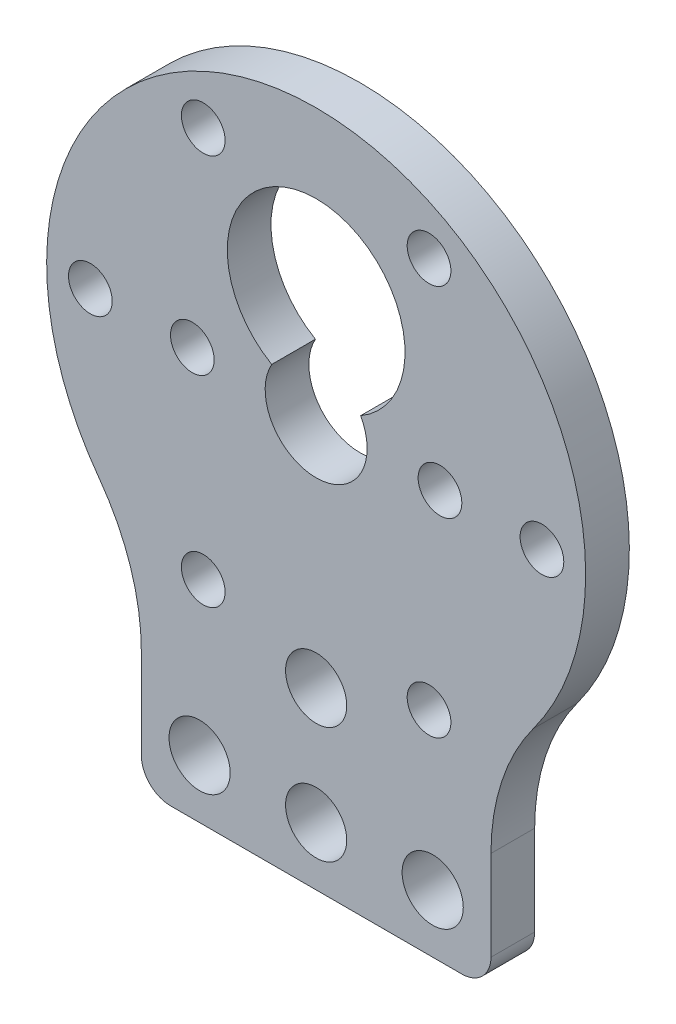
SolidWorks part; units mm, degrees
ref_plane "Front Plane" through (0, 0, 0) normal (0, 0, 1) x (1, 0, 0)
ref_plane "Top Plane" through (0, 0, 0) normal (0, 1, 0) x (1, 0, 0)
ref_plane "Right Plane" through (0, 0, 0) normal (1, 0, 0) x (0, 0, -1)
sketch "Sketch2" plane through (0, 0, 0) normal (0, 0, 1) x (1, 0, 0)
  line L0 (0, -28) -> (12, -28)
  line L1 (0, -28) -> (-12, -28)
  line L2 (-12, -28) -> (-12, -14.0801)
  line L3 (12, -28) -> (12, -14.0801)
  arc A0 (-3.0498, 1.7171) -> (3.0498, 1.7171) centre (0, 0) ccw
  arc A1 (12, -14.0801) -> (-12, -14.0801) centre (0, 0) ccw
  circle A2 centre (0, 0) radius 15.5 construction
  arc A3 (3.0498, 1.7171) -> (-3.0498, 1.7171) centre (0, 7) ccw
  point P7 (0, -28)
  dimension "D1" = 7
  dimension "D2" = 37
  dimension "D3" = 31
  dimension "D4" = 12.2
  dimension "D5" = 28
  dimension "D6" = 24
  dimension "D7" = 7
extrude "Boss-Extrude1" add sketch "Sketch2" along normal blind 3
hole_wizard "Ø3.0 (3) Diameter Hole2" positions "Sketch4" profile "Sketch3" hole size "Ø3.0" standard "ANSI Metric" end condition through all
sketch "Sketch4" plane through (0, 0, 3) normal (0, 0, 1) x (1, 0, 0)
  circle A0 centre (0, 0) radius 15.5 construction
  point P0 (15.5, 0)
  dimension "D1" = 31
sketch "Sketch3" plane through (15.5, 0, 3) normal (1, 0, 0) x (0, -1, 0)
  line L0 (0, 0) -> (0, 3)
  line L1 (0, 3) -> (1.5, 3)
  line L2 (1.5, 3) -> (1.5, 0)
  line L5 (1.5, 0) -> (0, 0)
  line L11 (0, -6.35) -> (0, 107.95) construction
  dimension "Thru Hole Dia." = 3
  dimension "Thru Hole Depth" = 3
ref_axis "Axis1" through (0, 0, -0.15) along (0, 0, 1)
pattern_circular "CirPattern1" count 6 over 360 about axis through (0, 0, -0.15) along (0, 0, 1) of "Ø3.0 (3) Diameter Hole2"
hole_wizard "Ø4.2 (4.2) Diameter Hole1" positions "Sketch6" profile "Sketch5" hole size "Ø4.2" standard "ANSI Metric" end condition through all
sketch "Sketch6" plane through (0, 0, 3) normal (0, 0, 1) x (1, 0, 0)
  point P0 (0, -16)
  point P2 (0, -24)
  point P4 (8, -24)
  point P6 (-8, -24)
  dimension "D1" = 16
  dimension "D2" = 8
  dimension "D3" = 8
  dimension "D4" = 8
sketch "Sketch5" plane through (0, -16, 3) normal (1, 0, 0) x (0, -1, 0)
  line L0 (0, 0) -> (0, 3)
  line L1 (0, 3) -> (2.1, 3)
  line L2 (2.1, 3) -> (2.1, 0)
  line L5 (2.1, 0) -> (0, 0)
  line L11 (0, -6.35) -> (0, 107.95) construction
  dimension "Thru Hole Dia." = 4.2
  dimension "Thru Hole Depth" = 3
hole_wizard "Ø3.0 (3) Diameter Hole1" positions "Sketch8" profile "Sketch7" hole size "Ø3.0" standard "ANSI Metric" end condition through all
sketch "Sketch8" plane through (0, 0, 3) normal (0, 0, 1) x (1, 0, 0)
  point P0 (8.5, 0)
  point P2 (-8.5, 0)
  dimension "D1" = 8.5
  dimension "D2" = 8.5
sketch "Sketch7" plane through (8.5, 0, 3) normal (1, 0, 0) x (0, -1, 0)
  line L0 (0, 0) -> (0, 3)
  line L1 (0, 3) -> (1.5, 3)
  line L2 (1.5, 3) -> (1.5, 0)
  line L5 (1.5, 0) -> (0, 0)
  line L11 (0, -6.35) -> (0, 107.95) construction
  dimension "Thru Hole Dia." = 3
  dimension "Thru Hole Depth" = 3
fillet "Fillet1" radius 15 2 edges at (12, -14.0801, 1.5) (-12, -14.0801, 1.5)
fillet "Fillet2" radius 2 2 edges at (12, -28, 1.5) (-12, -28, 1.5)
